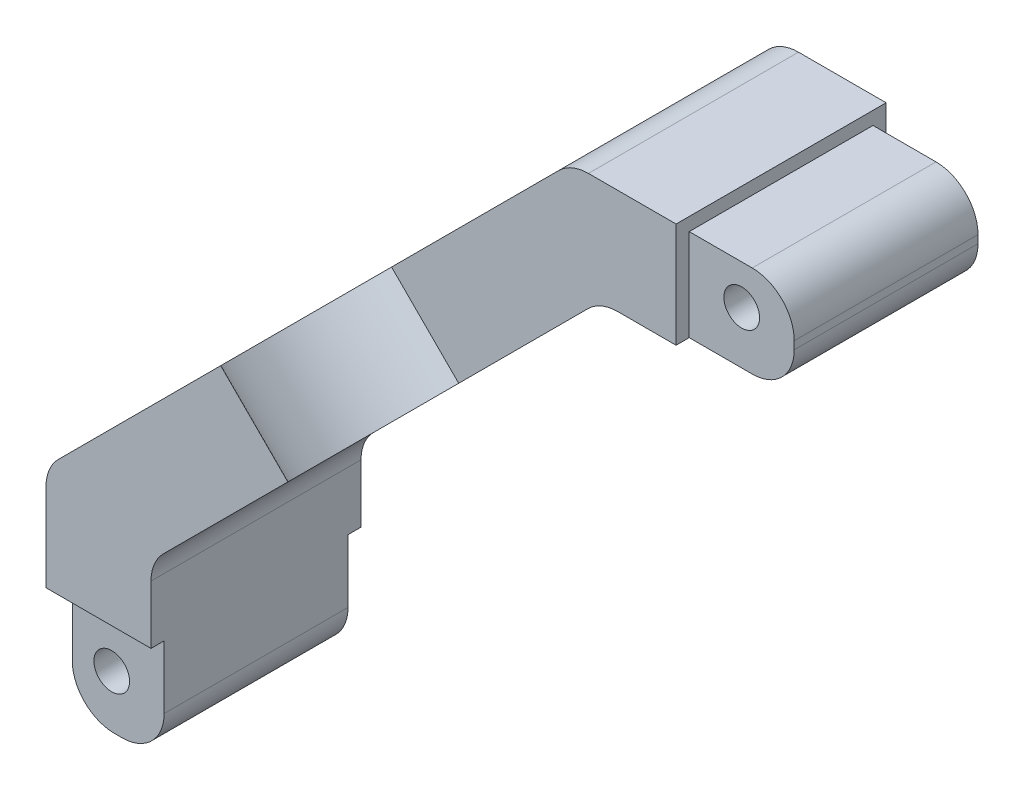
SolidWorks part; units mm, degrees
ref_plane "Front Plane" through (0, 0, 0) normal (0, 0, 1) x (1, 0, 0)
ref_plane "Top Plane" through (0, 0, 0) normal (0, 1, 0) x (1, 0, 0)
ref_plane "Right Plane" through (0, 0, 0) normal (1, 0, 0) x (0, 0, -1)
sketch "Sketch1" plane through (0, 0, 0) normal (0, 0, 1) x (1, 0, 0)
  line L0 (0, 0) -> (381, 0)
  line L1 (0, 0) -> (0, -381)
  line L2 (0, -12.7) -> (195.9668, -12.7)
  line L3 (15.1739, -73.5456) -> (73.5456, -15.1739)
  line L4 (15.1739, -73.5456) -> (33.1344, -91.5061)
  line L5 (33.1344, -91.5061) -> (91.5061, -33.1344)
  line L6 (73.5456, -15.1739) -> (91.5061, -33.1344)
  line L7 (15.1739, -73.5456) -> (91.5061, -33.1344) construction
  line L8 (33.1344, -91.5061) -> (73.5456, -15.1739) construction
  line L9 (12.7, 0) -> (12.7, -150.5133)
  line L10 (38.0736, -100.9354) -> (65.0143, -73.9946)
  line L15 (38.0736, -100.9354) -> (42.5637, -105.4255)
  line L16 (65.0143, -73.9946) -> (69.5045, -78.4847)
  line L21 (42.5637, -105.4255) -> (69.5045, -78.4847)
  line L22 (73.9946, -65.0143) -> (100.9354, -38.0736)
  line L27 (73.9946, -65.0143) -> (78.4847, -69.5045)
  line L28 (100.9354, -38.0736) -> (105.4255, -42.5637)
  line L29 (78.4847, -69.5045) -> (105.4255, -42.5637)
  line L30 (65.0143, -73.9946) -> (73.9946, -65.0143)
  line L31 (65.0143, -73.9946) -> (69.5045, -78.4847)
  line L32 (73.9946, -65.0143) -> (78.4847, -69.5045)
  line L33 (69.5045, -78.4847) -> (78.4847, -69.5045)
  line L34 (88.9, 0) -> (88.9, -25.4)
  line L35 (88.9, -25.4) -> (96.0842, -32.5842)
  line L36 (96.0842, -32.5842) -> (32.504, -96.1644)
  line L37 (0, -88.9) -> (25.4, -88.9)
  line L38 (25.4, -88.9) -> (32.504, -96.1644)
  line L39 (67.0392, -12.7) -> (12.7, -67.0392)
  line L40 (0, -63.5) -> (63.5, 0)
  line L41 (42.5637, -109.0176) -> (109.0176, -42.5637)
  line L42 (42.5637, -109.0176) -> (34.4815, -100.9354)
  line L43 (109.0176, -42.5637) -> (100.9354, -34.4815)
  line L44 (34.4815, -100.9354) -> (100.9354, -34.4815)
  line L45 (127, 0) -> (127, -50.8)
  line L46 (0, -127) -> (50.8, -127)
  line L47 (50.8, -127) -> (127, -50.8)
  line L48 (127, -1.5875) -> (88.9, -1.5875)
  line L49 (1.5875, -88.9) -> (1.5875, -127)
  point P3 (53.34, -53.34)
  point P33 (63.5, 0)
  point P34 (0, -63.5)
  dimension "D1" = 381
  dimension "D2" = 381
  dimension "D3" = 82.55
  dimension "D4" = 25.4
  dimension "D5" = 45
  dimension "D6" = 53.34
  dimension "D7" = 53.34
  dimension "D8" = 12.7
  dimension "D9" = 12.7
  dimension "D10" = 38.1
  dimension "D11" = 38.1
  dimension "D12" = 12.7
  dimension "D13" = 6.35
  dimension "D14" = 6.35
  dimension "D15" = 6.35
  dimension "D16" = 45
  dimension "D17" = 16.51
  dimension "D18" = 12.7
  dimension "D19" = 12.7
  dimension "D20" = 6.35
  dimension "D21" = 88.9
  dimension "D22" = 25.4
  dimension "D23" = 25.4
  dimension "D24" = 88.9
  dimension "D25" = 10.16
  dimension "D26" = 135
  dimension "D27" = 89.916
  dimension "D28" = 6.35
  dimension "D29" = 63.5
  dimension "D30" = 63.5
  dimension "D31" = 2.54
  dimension "D32" = 2.54
  dimension "D33" = 2.54
  dimension "D34" = 2.54
  dimension "D35" = 127
  dimension "D36" = 127
  dimension "D37" = 50.8
  dimension "D38" = 50.8
  dimension "D39" = 1.5875
  dimension "D40" = 1.5875
extrude "Boss-Extrude1" add sketch "Sketch1" along normal blind 25.4 contours L40 L9 L39 L2 | L40 L2 L34 L0 | L40 L1 L37 L9 region at (72.8133, -6.7733, 0) region at (6.7733, -72.8133, 0) region at (36.0475, -36.0475, 0)
sketch "Sketch2" plane through (0, 0, 25.4) normal (0, 0, 1) x (1, 0, 0)
  line L2 (88.9, 0) -> (76.2, 0)
  line L3 (88.9, 0) -> (88.9, -1.5875)
  line L4 (88.9, -1.5875) -> (76.2, -1.5875)
  line L5 (76.2, 0) -> (76.2, -1.5875)
  line L6 (0, -88.9) -> (1.5875, -88.9)
  line L7 (0, -88.9) -> (0, -76.2)
  line L8 (0, -76.2) -> (1.5875, -76.2)
  line L9 (1.5875, -88.9) -> (1.5875, -76.2)
  circle A0 centre (82.55, -6.3627) radius 2.159
  circle A1 centre (6.3627, -82.55) radius 2.159
  dimension "D1" = 4.318
  dimension "D2" = 4.318
  dimension "D3" = 82.55
  dimension "D4" = 82.55
  dimension "D5" = 4.7752
  dimension "D6" = 4.7752
  dimension "D7" = 1.5875
  dimension "D8" = 1.5875
  dimension "D9" = 12.7
  dimension "D10" = 12.7
extrude "Cut-Extrude1" cut sketch "Sketch2" against normal blind 25.4
sketch "Sketch3" plane through (0, -88.9, 0) normal (0, -1, 0) x (1, 0, 0)
  line L0 (0, 0) -> (0, 25.4) construction
  line L1 (12.7, 25.4) -> (0, 25.4)
  line L2 (12.7, 25.4) -> (12.7, 23.8125)
  line L3 (12.7, 23.8125) -> (0, 23.8125)
  line L4 (0, 25.4) -> (0, 23.8125)
  line L6 (12.7, 0) -> (0, 0)
  line L7 (12.7, 0) -> (12.7, 1.5748)
  line L8 (12.7, 1.5748) -> (0, 1.5748)
  line L9 (0, 0) -> (0, 1.5748)
  dimension "D1" = 1.5875
  dimension "D2" = 1.5748
extrude "Cut-Extrude2" cut sketch "Sketch3" against normal blind 12.7
sketch "Sketch4" plane through (88.9, 0, 0) normal (1, 0, 0) x (0, 0, -1)
  line L0 (0, 0) -> (-25.4, 0) construction
  line L1 (0, -12.7) -> (-1.5875, -12.7)
  line L2 (0, -12.7) -> (0, 0)
  line L3 (0, 0) -> (-1.5875, 0)
  line L4 (-1.5875, -12.7) -> (-1.5875, 0)
  line L6 (-25.4, -12.7) -> (-23.8125, -12.7)
  line L7 (-25.4, -12.7) -> (-25.4, 0)
  line L8 (-25.4, 0) -> (-23.8125, 0)
  line L9 (-23.8125, -12.7) -> (-23.8125, 0)
  dimension "D1" = 1.5875
  dimension "D2" = 1.5875
extrude "Cut-Extrude3" cut sketch "Sketch4" against normal blind 12.7
sketch3d "3DSketch1"
  line L0 (67.0392, -12.7, 0) -> (67.0392, -12.7, 25.4)
  line L1 (12.7, -67.0392, 0) -> (12.7, -67.0392, 25.4)
  line L2 (12.7, -67.0392, 0) -> (12.7, -76.2, 0) construction
  line L3 (12.7, -67.0392, 12.7) -> (67.0392, -12.7, 12.7)
  circle A0 centre (39.8696, -39.8696, 12.7) radius 11.1125
  circle A1 centre (39.8696, -39.8696, 12.7) radius 19.05
  point P2 (32.0119, -32.0119, 12.7)
  point P16 (26.3992, -26.3992, 12.7)
  dimension "D1" = 22.225
  dimension "D3" = 38.1
  dimension "D2" = 12.7
extrude "Boss-Extrude2" add sketch "3DSketch1" along direction (-0.7071, 0.7071, 0) on the side of the normal up to surface (11.4829 mm away) contours A1
extrude "Cut-Extrude4" cut sketch "3DSketch1<4>" along direction (0.7071, -0.7071, 0) on the side of the normal up to surface (11.4829 mm away) contours A0
sketch3d "3DSketch1<4>" same geometry as "3DSketch1"
ref_plane "Plane1" through (31.75, -31.75, 0) normal (-0.7071, 0.7071, 0) x (0, 0, 1)
sketch "Sketch5" plane through (31.75, -31.75, 0) normal (-0.7071, 0.7071, 0) x (0, 0, 1)
  circle A0 centre (12.7, 0) radius 11.1125
  circle A1 centre (12.7, 0) radius 4.572
  dimension "D1" = 9.144
extrude "Boss-Extrude3" add sketch "Sketch5" against normal blind 3.81
fillet "Fillet1" radius 5.08 8 edges at (67.0392, -12.7, 12.7) (12.7, -67.0392, 12.7) (12.7, -88.9, 12.6937) (1.5875, -88.9, 12.6936) (0, -63.5, 12.7) (63.5, 0, 12.7) (88.9, -12.7, 12.7) (88.9, -1.5875, 12.7)
fillet "Fillet2" radius 1.016 1 edges at (32.0119, -47.7273, 12.7)
